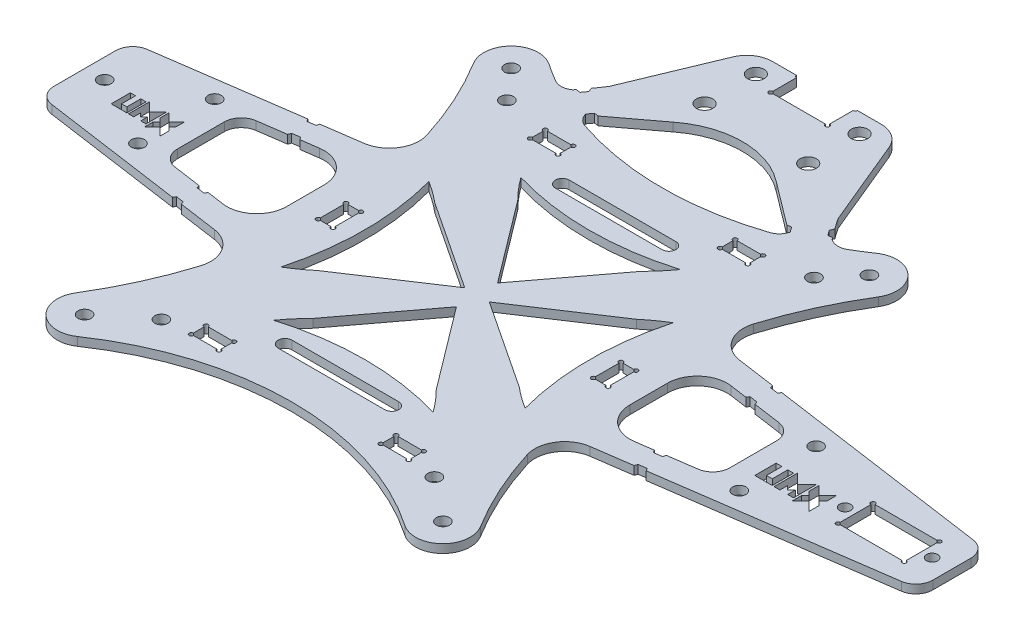
SolidWorks part; units mm, degrees
other "细节项目1" parameters "D5"=3.1, "D18"=3.2, "D24"=1.84, "D6"=8.6708, "D11"=4.977, "D15"=5.1762, "D16"=1.6515, "D17"=3.1, "D21"=13.484, "D14"=3.1, "D32"=6.4038, "D1"=40.7355, "D2"=35.8432, "D3"=28, "D4"=40.1699, "D7"=36.5, "D8"=41.25, "D9"=46.5, "D10"=20, "D12"=32.5, "D13"=87.0157, "D19"=3.5, "D20"=2.5, "D22"=0.15, "D23"=0.525, "D25"=70.5, "D26"=9, "D27"=9, "D28"=9.5, "D29"=135, "D30"=15.9142, "D31"=16.8571, "D33"=75.3972, "D34"=18.2471, "D35"=25, "D36"=25
other "细节项目2"
material "PPS"
ref_plane "前视基准面" through (0, 0, 0) normal (0, 0, 1) x (1, 0, 0)
ref_plane "上视基准面" through (0, 0, 0) normal (0, 1, 0) x (1, 0, 0)
ref_plane "右视基准面" through (0, 0, 0) normal (1, 0, 0) x (0, 0, -1)
sketch "草图1" plane through (0, 0, 0) normal (0, 1, 0) x (1, 0, 0)
  line L3 (-133.7177, 0) -> (146.3754, 0) construction
  line L56 (0, 96.0639) -> (0, -115.1457) construction
  line L65 (-25.5, 41.5) -> (-19, 41.5)
  line L66 (-34, 3.25) -> (-30.5, 3.25)
  line L70 (-34, 3.25) -> (-34, -3.25)
  line L76 (-34, -3.25) -> (-30.5, -3.25)
  line L80 (-30.5, 3.25) -> (-30.5, -3.25)
  line L81 (-25.5, -38) -> (-19, -38)
  line L82 (-25.5, -38) -> (-25.5, -41.5)
  line L83 (-25.5, -41.5) -> (-19, -41.5)
  line L84 (-19, -38) -> (-19, -41.5)
  line L85 (-19, 38) -> (-19, 41.5)
  line L86 (-25.5, 38) -> (-19, 38)
  line L142 (-25.5, 38) -> (-25.5, 41.5)
  line L143 (25.5, 38) -> (25.5, 41.5)
  line L144 (25.5, 38) -> (19, 38)
  line L145 (19, 38) -> (19, 41.5)
  line L146 (19, -38) -> (19, -41.5)
  line L147 (25.5, -41.5) -> (19, -41.5)
  line L148 (25.5, -38) -> (25.5, -41.5)
  line L149 (25.5, -38) -> (19, -38)
  line L150 (30.5, 3.25) -> (30.5, -3.25)
  line L151 (34, -3.25) -> (30.5, -3.25)
  line L152 (34, 3.25) -> (34, -3.25)
  line L153 (34, 3.25) -> (30.5, 3.25)
  line L154 (25.5, 41.5) -> (19, 41.5)
  line L155 (77.65, -2.1518) -> (77.65, -4) construction
  line L156 (74.85, 4) -> (77.65, 4) construction
  line L157 (74.85, 4) -> (74.85, 2.1768) construction
  line L158 (74.85, -4) -> (77.65, -4) construction
  line L159 (77.65, 4) -> (77.65, 2.1518) construction
  line L160 (74.85, -2.1768) -> (74.85, -4) construction
  line L161 (96.5, 7.6653) -> (96.5, -9.1503) construction
  line L162 (88.75, 4.1) -> (104.25, 4.1)
  line L163 (88.75, 4.1) -> (88.75, -4.1)
  line L164 (88.75, -4.1) -> (104.25, -4.1)
  line L165 (104.25, 4.1) -> (104.25, -4.1)
  line L166 (-96.5, 7.6653) -> (-96.5, -9.1503) construction
  line L171 (-74.85, -2.1768) -> (-74.85, -4) construction
  line L172 (-77.65, 4) -> (-77.65, 2.1518) construction
  line L173 (-74.85, -4) -> (-77.65, -4) construction
  line L174 (-74.85, 4) -> (-74.85, 2.1768) construction
  line L175 (-74.85, 4) -> (-77.65, 4) construction
  line L176 (-77.65, -2.1518) -> (-77.65, -4) construction
  line L177 (111.35, 7.9303) -> (111.35, -7.9303)
  line L178 (111.35, 7.9303) -> (36.25, 18.6361)
  line L179 (111.35, -7.9303) -> (36.25, -18.6361)
  line L184 (14.4296, 23.978) -> (0, 4.8247)
  line L186 (-14.4296, 23.978) -> (0, 4.8247)
  line L187 (23.6257, -13.733) -> (2.8757, 0)
  line L188 (23.6257, 13.733) -> (2.8757, 0)
  line L191 (-91.953, 10.6955) -> (-91.953, -10.6955)
  line L192 (-36.25, 18.6361) -> (-91.953, 10.6955)
  line L193 (-91.953, -10.6955) -> (-36.25, -18.6361)
  line L195 (-64.75, -8.9672) -> (-64.75, 8.9672)
  line L196 (-64.75, 8.9672) -> (-40.25, 12.4598)
  line L197 (-40.25, 12.4598) -> (-40.25, -12.4598)
  line L198 (-64.75, -8.9672) -> (-40.25, -12.4598)
  line L199 (64.75, 8.9672) -> (40.25, 12.4598)
  line L200 (40.25, 12.4598) -> (40.25, -12.4598)
  line L201 (64.75, -8.9672) -> (40.25, -12.4598)
  line L202 (64.75, 8.9672) -> (64.75, -8.9672)
  line L211 (-23.6257, 13.733) -> (-2.8757, 0)
  line L212 (-23.6257, -13.733) -> (-2.8757, 0)
  line L213 (-14.4296, -23.978) -> (0, -4.8247)
  line L214 (14.4296, -23.978) -> (0, -4.8247)
  line L215 (12.5, 32.5) -> (-12.5, 32.5) construction
  line L216 (12.5, 30.875) -> (-12.5, 30.875)
  line L217 (12.5, 34.125) -> (-12.5, 34.125)
  line L218 (12.5, -32.5) -> (-12.5, -32.5) construction
  line L219 (12.5, -30.875) -> (-12.5, -30.875)
  line L220 (12.5, -34.125) -> (-12.5, -34.125)
  circle A0 centre (-36, 43) radius 1.55
  circle A1 centre (-32, -42) radius 1.55
  circle A2 centre (32, -42) radius 1.55
  circle A3 centre (36, 43) radius 1.55
  circle A4 centre (42, 50) radius 1.55
  circle A5 centre (42, -50) radius 1.55
  circle A6 centre (-42, -50) radius 1.55
  circle A7 centre (-42, 50) radius 1.55
  arc A8 (74.85, 2.1768) -> (74.85, -2.1768) centre (76.2307, 0) ccw construction
  arc A9 (77.65, -2.1518) -> (77.65, 2.1518) centre (76.2307, 0) ccw construction
  circle A10 centre (106.7, 0) radius 1.3
  circle A11 centre (86.3, 0) radius 1.3
  arc A14 (-77.65, -2.1518) -> (-77.65, 2.1518) centre (-76.2307, 0) cw construction
  arc A15 (-74.85, 2.1768) -> (-74.85, -2.1768) centre (-76.2307, 0) cw construction
  arc A18 (-38.3898, 55.2892) -> (38.3898, 55.2892) centre (0, 111.5317) ccw
  arc A20 (47.4575, 46.6496) -> (36.25, 18.6361) centre (123.4458, 0) ccw
  arc A21 (47.4575, 46.6496) -> (38.3898, 55.2892) centre (42, 50) ccw
  arc A22 (-38.3898, -55.2892) -> (38.3898, -55.2892) centre (0, -111.5317) cw
  arc A23 (47.4575, -46.6496) -> (36.25, -18.6361) centre (123.4458, 0) cw
  arc A24 (47.4575, -46.6496) -> (38.3898, -55.2892) centre (42, -50) cw
  arc A26 (-47.4575, -46.6496) -> (-38.3898, -55.2892) centre (-42, -50) ccw
  arc A27 (-47.4575, -46.6496) -> (-36.25, -18.6361) centre (-123.4458, 0) ccw
  arc A28 (-47.4575, 46.6496) -> (-38.3898, 55.2892) centre (-42, 50) cw
  arc A30 (-47.4575, 46.6496) -> (-36.25, 18.6361) centre (-123.4458, 0) cw
  arc A34 (-14.4296, 23.978) -> (-18.6871, 28.9822) centre (14.4807, 52.8883) cw
  arc A35 (-18.6871, 28.9822) -> (18.6871, 28.9822) centre (0, 91.9966) ccw
  arc A36 (14.4296, 23.978) -> (18.6871, 28.9822) centre (-14.4807, 52.8883) ccw
  arc A37 (23.6257, 13.733) -> (28.6529, 17.3535) centre (49.9637, -17.5386) cw
  arc A38 (28.6529, 17.3535) -> (28.6529, -17.3535) centre (92.8745, 0) ccw
  arc A39 (23.6257, -13.733) -> (28.6529, -17.3535) centre (49.436, 16.806) ccw
  circle A43 centre (70.5, 9) radius 1.55
  circle A44 centre (70.5, -9) radius 1.55
  circle A45 centre (-70.5, -9) radius 1.55
  circle A46 centre (-70.5, 9) radius 1.55
  circle A47 centre (-87.3, 0) radius 1.55
  arc A48 (-23.6257, -13.733) -> (-28.6529, -17.3535) centre (-49.436, 16.806) cw
  arc A49 (-28.6529, 17.3535) -> (-28.6529, -17.3535) centre (-92.8745, 0) cw
  arc A50 (-23.6257, 13.733) -> (-28.6529, 17.3535) centre (-49.9637, -17.5386) ccw
  arc A51 (14.4296, -23.978) -> (18.6871, -28.9822) centre (-14.4807, -52.8883) cw
  arc A52 (-18.6871, -28.9822) -> (18.6871, -28.9822) centre (0, -91.9966) cw
  arc A53 (-14.4296, -23.978) -> (-18.6871, -28.9822) centre (14.4807, -52.8883) ccw
  arc A54 (12.5, 30.875) -> (12.5, 34.125) centre (12.5, 32.5) ccw
  arc A55 (-12.5, 34.125) -> (-12.5, 30.875) centre (-12.5, 32.5) ccw
  arc A56 (12.5, -30.875) -> (12.5, -34.125) centre (12.5, -32.5) cw
  arc A57 (-12.5, -34.125) -> (-12.5, -30.875) centre (-12.5, -32.5) cw
  point P81 (-34, 0)
  point P118 (0, 0)
  point P140 (-40.25, 0)
  point P149 (-64.75, 0)
  point P150 (0, 32.5)
  point P158 (0, -32.5)
  dimension "D6" = 3.1
  dimension "D16" = 2.6
  dimension "D21" = 3.1
  dimension "D14" = 3.1
  dimension "D32" = 6.4038
  dimension "D1" = 6.5
  dimension "D2" = 3.5
  dimension "D3" = 30.5
  dimension "D4" = 19
  dimension "D5" = 38
  dimension "D7" = 32
  dimension "D8" = 42
  dimension "D9" = 43
  dimension "D10" = 36
  dimension "D11" = 50
  dimension "D12" = 42
  dimension "D13" = 2.8
  dimension "D15" = 74.85
  dimension "D17" = 15.5
  dimension "D18" = 8.2
  dimension "D19" = 2.45
  dimension "D20" = 96.5
  dimension "D22" = 9
  dimension "D23" = 70.5
  dimension "D25" = 5.55
  dimension "D26" = 5.75
  dimension "D27" = 6.25
  dimension "D28" = 4
  dimension "D29" = 2.45
  dimension "D24" = 87.3
  dimension "D30" = 4.653
  dimension "D31" = 4.65
  dimension "D33" = 72.5
  dimension "D34" = 25
  dimension "D35" = 32.5
  dimension "D36" = 3.25
extrude "凸台-拉伸1" add sketch "草图1" along normal blind 2
fillet "圆角1" radius 4 8 edges at (111.35, 1, -7.9303) (111.35, 1, 7.9303) (-91.953, 1, 10.6955) (-91.953, 1, -10.6955) (-64.75, 1, 8.9672) (-64.75, 1, -8.9672) (64.75, 1, 8.9672) (64.75, 1, -8.9672)
fillet "圆角2" radius 7 8 edges at (36.25, 1, -18.6361) (36.25, 1, 18.6361) (-36.25, 1, 18.6361) (-36.25, 1, -18.6361) (40.25, 1, 12.4598) (40.25, 1, -12.4598) (-40.25, 1, 12.4598) (-40.25, 1, -12.4598)
sketch "光流接口-修改" plane through (0, 0, 0) normal (0, 1, 0) x (1, 0, 0)
  line L0 (30.4025, 52.8577) -> (32.0373, 51.0287)
  line L1 (-32.0373, 51.0287) -> (-30.4025, 52.8577)
  line L2 (-6.65, 82.03) -> (-6.65, 75.53)
  line L3 (-6.65, 75.53) -> (-0.15, 75.53)
  line L4 (-0.15, 75.53) -> (-0.15, 82.03) construction
  line L5 (-12.7467, 82.03) -> (-6.65, 82.03)
  line L6 (-0.15, 75.53) -> (0.15, 75.53)
  line L7 (6.65, 75.53) -> (0.15, 75.53)
  line L8 (0.15, 75.53) -> (0.15, 82.03) construction
  line L9 (6.65, 82.03) -> (6.65, 75.53)
  line L10 (12.7467, 82.03) -> (6.65, 82.03)
  line L11 (0, 62.25) -> (29.4648, 62.25) construction
  line L12 (12.079, 58.0811) -> (29.4648, 44.9866)
  line L13 (18.3322, 78.3014) -> (26.8267, 57.8446)
  line L14 (0, -39.4607) -> (0, 39.4607) construction
  line L15 (-18.3322, 78.3014) -> (-26.8267, 57.8446)
  line L16 (-12.079, 58.0811) -> (-29.4648, 44.9866)
  line L17 (-12.7467, 82.03) -> (12.7467, 82.03) construction
  circle A38 centre (-12.15, 77.53) radius 1.925
  circle A39 centre (-12.15, 65.5) radius 1.925
  circle A40 centre (12.15, 65.5) radius 1.925
  circle A41 centre (12.15, 77.53) radius 1.925
  circle A42 centre (-36, 43) radius 1.55
  circle A43 centre (36, 43) radius 1.55
  arc A44 (-37.8248, 46.5595) -> (-32.3705, 41.3187) centre (-36, 43) ccw
  arc A45 (37.8248, 46.5595) -> (32.3705, 41.3187) centre (36, 43) cw
  arc A46 (32.3705, 41.3187) -> (29.4648, 44.9866) centre (23.2968, 37.1154) ccw
  arc A47 (37.8248, 46.5595) -> (32.0373, 51.0287) centre (46.9489, 64.357) cw
  arc A48 (-12.079, 58.0811) -> (12.079, 58.0811) centre (0, 42.6665) cw
  arc A49 (26.8267, 57.8446) -> (30.4025, 52.8577) centre (93.5808, 101.9342) ccw
  arc A50 (12.7467, 82.03) -> (18.3322, 78.3014) centre (12.7467, 75.9821) cw
  arc A51 (-12.7467, 82.03) -> (-18.3322, 78.3014) centre (-12.7467, 75.9821) ccw
  arc A52 (-26.8267, 57.8446) -> (-30.4025, 52.8577) centre (-93.5808, 101.9342) cw
  arc A53 (-37.8248, 46.5595) -> (-32.0373, 51.0287) centre (-46.9489, 64.357) ccw
  arc A54 (-32.3705, 41.3187) -> (-29.4648, 44.9866) centre (-23.2968, 37.1154) cw
  arc A55 (-37.8248, 46.5595) -> (-32.3705, 41.3187) centre (-36, 43) ccw
  circle A56 centre (-36, 43) radius 1.55
  point P10 (0, 82.03)
  point P13 (-18.3322, 78.3014)
  dimension "D4" = 3.85
  dimension "D9" = 3.25
  dimension "D1" = 12.03
  dimension "D2" = 24.3
  dimension "D3" = 65.5
  dimension "D5" = 5.5
  dimension "D6" = 6.5
  dimension "D7" = 6.5
  dimension "D8" = 4.5
extrude "凸台-拉伸2" add sketch "光流接口-修改" along normal up to surface (2 mm away) from surface at 0 contours A48 L14 L17 A51 L15 A52 L1 A53 A44 A54 L16 A42 A39 A38 | L14 A48 L12 A46 A45 A47 L0 A49 L13 A50 L17 A40 A41 A43
sketch "线槽-草图" plane through (0, 0, 0) normal (0, 1, 0) x (1, 0, 0)
  line L1 (107.9145, 8.4201) -> (44.0177, 17.5288) construction
  line L5 (57.8515, 15.5567) -> (57.0683, 10.0623) construction
  line L6 (53.6304, 11.2089) -> (53.5387, 10.5654) construction
  line L7 (57.4599, 12.8095) -> (49.4026, 13.9581) construction
  line L8 (54.5679, 11.0753) -> (52.693, 11.3426)
  line L9 (54.7762, 10.389) -> (54.5679, 11.0753)
  line L10 (52.3012, 10.7418) -> (54.7762, 10.389)
  line L11 (52.693, 11.3426) -> (52.3012, 10.7418)
  line L12 (0, 0) -> (132.6638, 0) construction
  line L21 (0, -0.7474) -> (0, 57.4396) construction
  line L38 (61.3145, 9.457) -> (48.2379, 11.3211) construction
  line L39 (54.2302, 15.4164) -> (54.322, 16.0599) construction
  line L40 (53.2928, 15.55) -> (53.0845, 16.2363)
  line L41 (53.0845, 16.2363) -> (55.5595, 15.8835)
  line L42 (55.5595, 15.8835) -> (55.1677, 15.2828)
  line L43 (55.1677, 15.2828) -> (53.2928, 15.55)
  line L44 (-54.2302, 15.4164) -> (-54.322, 16.0599) construction
  line L45 (-57.4599, 12.8095) -> (-49.4026, 13.9581) construction
  line L46 (-53.6304, 11.2089) -> (-53.5387, 10.5654) construction
  line L47 (-57.8515, 15.5567) -> (-57.0683, 10.0623) construction
  line L48 (-55.1677, 15.2828) -> (-53.2928, 15.55)
  line L49 (-55.5595, 15.8835) -> (-55.1677, 15.2828)
  line L50 (-53.0845, 16.2363) -> (-55.5595, 15.8835)
  line L51 (-53.2928, 15.55) -> (-53.0845, 16.2363)
  line L52 (-52.693, 11.3426) -> (-52.3012, 10.7418)
  line L53 (-52.3012, 10.7418) -> (-54.7762, 10.389)
  line L54 (-54.7762, 10.389) -> (-54.5679, 11.0753)
  line L55 (-54.5679, 11.0753) -> (-52.693, 11.3426)
  line L56 (-57.8515, -15.5567) -> (-57.0683, -10.0623) construction
  line L57 (-53.6304, -11.2089) -> (-53.5387, -10.5654) construction
  line L58 (-57.4599, -12.8095) -> (-49.4026, -13.9581) construction
  line L59 (-54.2302, -15.4164) -> (-54.322, -16.0599) construction
  line L60 (-54.5679, -11.0753) -> (-52.693, -11.3426)
  line L61 (-54.7762, -10.389) -> (-54.5679, -11.0753)
  line L62 (-52.3012, -10.7418) -> (-54.7762, -10.389)
  line L63 (-52.693, -11.3426) -> (-52.3012, -10.7418)
  line L64 (-53.2928, -15.55) -> (-53.0845, -16.2363)
  line L65 (-53.0845, -16.2363) -> (-55.5595, -15.8835)
  line L66 (-55.5595, -15.8835) -> (-55.1677, -15.2828)
  line L67 (-55.1677, -15.2828) -> (-53.2928, -15.55)
  line L68 (54.2302, -15.4164) -> (54.322, -16.0599) construction
  line L69 (57.4599, -12.8095) -> (49.4026, -13.9581) construction
  line L70 (53.6304, -11.2089) -> (53.5387, -10.5654) construction
  line L71 (57.8515, -15.5567) -> (57.0683, -10.0623) construction
  line L72 (55.1677, -15.2828) -> (53.2928, -15.55)
  line L73 (55.5595, -15.8835) -> (55.1677, -15.2828)
  line L74 (53.0845, -16.2363) -> (55.5595, -15.8835)
  line L75 (53.2928, -15.55) -> (53.0845, -16.2363)
  line L76 (52.693, -11.3426) -> (52.3012, -10.7418)
  line L77 (52.3012, -10.7418) -> (54.7762, -10.389)
  line L78 (54.7762, -10.389) -> (54.5679, -11.0753)
  line L79 (54.5679, -11.0753) -> (52.693, -11.3426)
  line L80 (29.3031, 54.3067) -> (93.5808, 101.9342) construction
  line L81 (28.5667, 55.3169) -> (28.1719, 54.3981)
  line L82 (28.1719, 54.3981) -> (29.0551, 53.1972)
  line L83 (29.0551, 53.1972) -> (30.0551, 53.3082)
  line L84 (29.3031, 54.3067) -> (23.1468, 49.7452) construction
  line L85 (25.1375, 48.2458) -> (12.079, 58.0811) construction
  line L86 (23.5935, 48.522) -> (22.1067, 50.5285)
  line L87 (22.1067, 50.5285) -> (23.1067, 50.6431)
  line L88 (23.1067, 50.6431) -> (23.9942, 49.4453)
  line L89 (23.9942, 49.4453) -> (23.5935, 48.522)
  line L90 (-29.3031, 54.3067) -> (-23.1468, 49.7452) construction
  line L91 (-23.9942, 49.4453) -> (-23.5935, 48.522)
  line L92 (-23.1067, 50.6431) -> (-23.9942, 49.4453)
  line L93 (-22.1067, 50.5285) -> (-23.1067, 50.6431)
  line L94 (-23.5935, 48.522) -> (-22.1067, 50.5285)
  line L95 (-29.0551, 53.1972) -> (-30.0551, 53.3082)
  line L96 (-28.1719, 54.3981) -> (-29.0551, 53.1972)
  line L97 (-28.5667, 55.3169) -> (-28.1719, 54.3981)
  arc A0 (28.5667, 55.3169) -> (30.0551, 53.3082) centre (93.5808, 101.9342) ccw
  arc A1 (26.8267, 57.8446) -> (30.4025, 52.8577) centre (93.5808, 101.9342) ccw construction
  arc A2 (-28.5667, 55.3169) -> (-30.0551, 53.3082) centre (-93.5808, 101.9342) cw
  point P47 (54.7762, 10.389)
  point P49 (28.5667, 55.3169)
  point P88 (23.5505, 50.0442)
  dimension "D5" = 1
  dimension "D1" = 2.5
  dimension "D2" = 115
  dimension "D3" = 0.65
  dimension "D4" = 2.5
  dimension "D6" = 1
  dimension "D7" = 120
  dimension "D8" = 120
  dimension "D9" = 1
extrude "线槽" cut sketch "线槽-草图" along normal through all
sketch "草图10" plane through (0, 0, 0) normal (0, 1, 0) x (1, 0, 0)
  line L0 (0, 0) -> (0, -66.7571) construction
  line L1 (-6.65, 75.53) -> (6.65, 75.53) construction
  circle A0 centre (-77.65, 4) radius 0.5 construction
  circle A1 centre (-74.85, 4) radius 0.5 construction
  circle A2 centre (-77.65, -4) radius 0.5 construction
  circle A3 centre (-74.85, -4) radius 0.5 construction
  circle A4 centre (-25.5, 41.5) radius 0.5
  circle A5 centre (-19, 41.5) radius 0.5
  circle A6 centre (-25.5, 38) radius 0.5
  circle A7 centre (-19, 38) radius 0.5
  circle A8 centre (-34, 3.25) radius 0.5
  circle A9 centre (-30.5, 3.25) radius 0.5
  circle A10 centre (-34, -3.25) radius 0.5
  circle A11 centre (-30.5, -3.25) radius 0.5
  circle A12 centre (-25.5, -38) radius 0.5
  circle A13 centre (-19, -38) radius 0.5
  circle A14 centre (-25.5, -41.5) radius 0.5
  circle A15 centre (-19, -41.5) radius 0.5
  circle A16 centre (19, -41.5) radius 0.5
  circle A17 centre (25.5, -41.5) radius 0.5
  circle A18 centre (19, -38) radius 0.5
  circle A19 centre (25.5, -38) radius 0.5
  circle A20 centre (30.5, -3.25) radius 0.5
  circle A21 centre (34, -3.25) radius 0.5
  circle A22 centre (30.5, 3.25) radius 0.5
  circle A23 centre (34, 3.25) radius 0.5
  circle A24 centre (19, 38) radius 0.5
  circle A25 centre (25.5, 38) radius 0.5
  circle A26 centre (19, 41.5) radius 0.5
  circle A27 centre (25.5, 41.5) radius 0.5
  circle A28 centre (74.85, -4) radius 0.5 construction
  circle A29 centre (77.65, -4) radius 0.5 construction
  circle A30 centre (74.85, 4) radius 0.5 construction
  circle A31 centre (77.65, 4) radius 0.5 construction
  circle A32 centre (88.75, 4.1) radius 0.5
  circle A33 centre (104.25, 4.1) radius 0.5
  circle A34 centre (88.75, -4.1) radius 0.5
  circle A35 centre (104.25, -4.1) radius 0.5
  circle A37 centre (-6.65, 75.53) radius 0.5
  circle A38 centre (6.65, 75.53) radius 0.5
  circle A39 centre (-6.65, 82.03) radius 0.5
  circle A40 centre (6.65, 82.03) radius 0.5
  dimension "D1" = 1
extrude "直角刀口" cut sketch "草图10" along normal through all
fillet "圆角6" radius 3.5 4 edges at (31.7859, 1, -51.31) (25.1375, 1, -48.2458) (-31.7859, 1, -51.31) (-25.1375, 1, -48.2458)
sketch "底部维修槽-草图" plane through (0, 0, 0) normal (0, 1, 0) x (1, 0, 0)
  line L0 (0, 0) -> (151.2551, 0) construction
  line L1 (0, 0) -> (0, 91.1633) construction
  line L2 (15.25, 15.25) -> (10, 10) construction
  line L3 (16.1339, 14.3661) -> (10.8839, 9.1161)
  line L4 (14.3661, 16.1339) -> (9.1161, 10.8839)
  line L5 (10, 10) -> (0, 0) construction
  line L6 (-15.25, 15.25) -> (-10, 10) construction
  line L7 (-16.1339, 14.3661) -> (-10.8839, 9.1161)
  line L8 (-14.3661, 16.1339) -> (-9.1161, 10.8839)
  line L9 (15.25, -15.25) -> (10, -10) construction
  line L10 (16.1339, -14.3661) -> (10.8839, -9.1161)
  line L11 (14.3661, -16.1339) -> (9.1161, -10.8839)
  line L12 (-15.25, -15.25) -> (-10, -10) construction
  line L13 (-16.1339, -14.3661) -> (-10.8839, -9.1161)
  line L14 (-14.3661, -16.1339) -> (-9.1161, -10.8839)
  arc A3 (16.1339, 14.3661) -> (14.3661, 16.1339) centre (15.25, 15.25) ccw
  arc A4 (9.1161, 10.8839) -> (10.8839, 9.1161) centre (10, 10) ccw
  arc A5 (-16.1339, 14.3661) -> (-14.3661, 16.1339) centre (-15.25, 15.25) cw
  arc A6 (-9.1161, 10.8839) -> (-10.8839, 9.1161) centre (-10, 10) cw
  arc A7 (16.1339, -14.3661) -> (14.3661, -16.1339) centre (15.25, -15.25) cw
  arc A8 (9.1161, -10.8839) -> (10.8839, -9.1161) centre (10, -10) cw
  arc A9 (-16.1339, -14.3661) -> (-14.3661, -16.1339) centre (-15.25, -15.25) ccw
  arc A10 (-9.1161, -10.8839) -> (-10.8839, -9.1161) centre (-10, -10) ccw
  point P6 (12.625, 12.625)
  point P14 (-12.625, 12.625)
  point P21 (12.625, -12.625)
  point P28 (-12.625, -12.625)
  dimension "D4" = 1.25
  dimension "D1" = 20
  dimension "D2" = 45
  dimension "D3" = 30.5
extrude "底部维修孔-不好看影响结构压缩了" [suppressed] cut sketch "底部维修槽-草图" along normal blind 10
sketch "文字-草图" plane through (0, 0, 0) normal (0, 1, 0) x (1, 0, 0)
  line L0 (100.1823, -4.1) -> (82.8841, -4.1) construction
  line L1 (89.25, -4.1) -> (103.75, -4.1) construction
  line L2 (82.8841, -4.1) -> (69.4115, -4.1) construction
  line L3 (69.4115, -4.1) -> (-69.3951, -4.1) construction
  line L4 (-69.3951, -4.1) -> (-85.0661, -4.1) construction
  text T0 "XMU" font "Sheeping Dogs" height 5
  text T1 "XMU" font "Sheeping Dogs" height 4.5
extrude "切除-拉伸1" cut sketch "文字-草图" along normal through all
